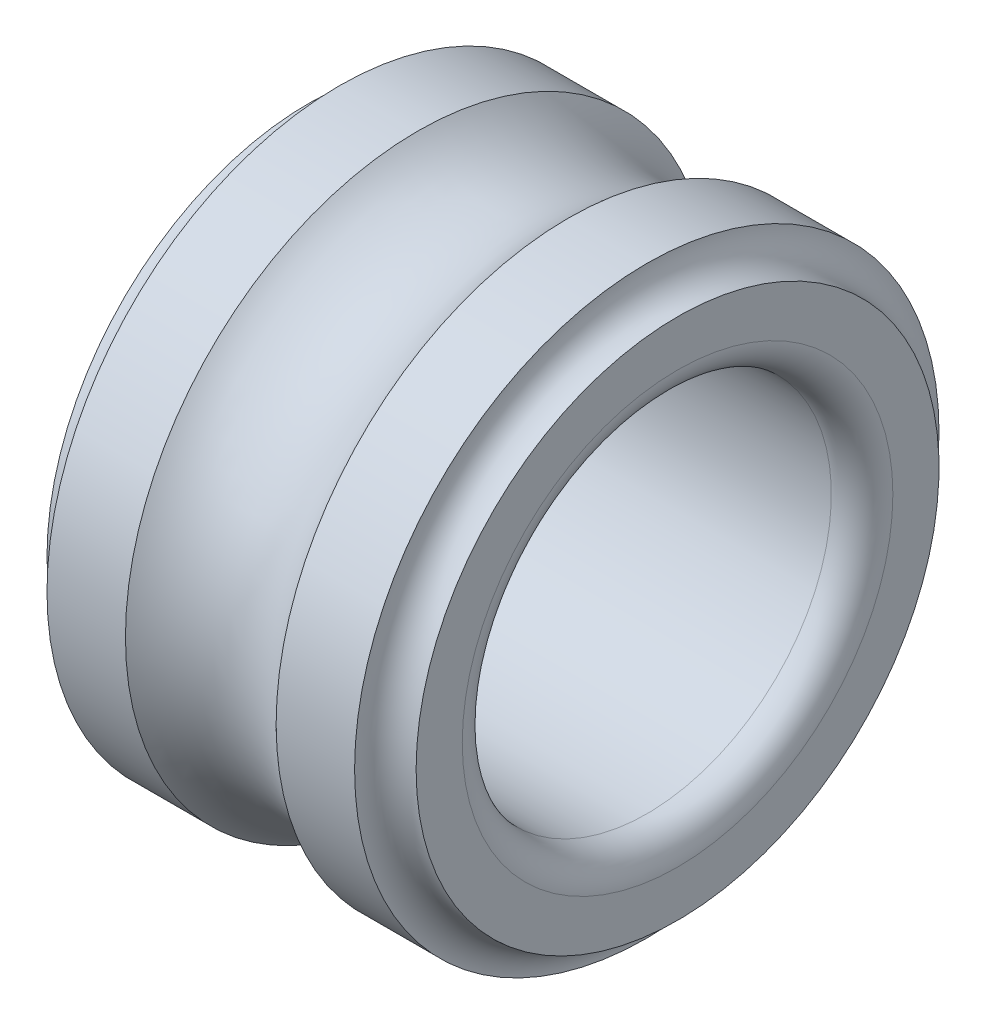
SolidWorks part; units mm, degrees
ref_plane "Front" through (0, 0, 0) normal (0, 0, 1) x (1, 0, 0)
ref_plane "Top" through (0, 0, 0) normal (0, 1, 0) x (1, 0, 0)
ref_plane "Right" through (0, 0, 0) normal (1, 0, 0) x (0, 0, -1)
sketch "Sketch1" plane through (0, 0, 0) normal (0, 0, 1) x (1, 0, 0)
  line L0 (-6, 6) -> (6, 6)
  line L1 (-6, 0) -> (6, 0)
  line L2 (-6, 0) -> (-6, 18)
  line L3 (-6, 18) -> (6, 18)
  line L4 (6, 0) -> (6, 18)
  line L5 (-6, 18) -> (6, 6)
  line L6 (-6, 14.5) -> (6, 14.5)
  line L7 (-6, 9.5) -> (6, 9.5)
  circle A0 centre (0, 12) radius 3.5
  dimension "D4" = 7
  dimension "D1" = 18
  dimension "D2" = 12
  dimension "D3" = 12
  dimension "D5" = 3.5
  dimension "D6" = 3.5
sketch "Sketch2" plane through (0, 0, 0) normal (0, 0, 1) x (1, 0, 0)
  line L0 (-6, 9.5) -> (6, 9.5) construction
  line L1 (-6, 9.5) -> (-2.4495, 9.5)
  line L2 (-6, 6) -> (6, 6) construction
  line L3 (-6, 0) -> (-6, 18) construction
  line L4 (6, 0) -> (6, 18) construction
  line L5 (-6, 0) -> (6, 0) construction
  line L6 (-5, 6) -> (5, 6)
  line L7 (-6, 7) -> (-6, 9.5)
  line L8 (6, 7) -> (6, 9.5)
  line L9 (-6, 0) -> (6, 0) construction
  line L10 (2.4495, 9.5) -> (6, 9.5)
  circle A0 centre (0, 12) radius 3.5 construction
  arc A1 (-2.4495, 9.5) -> (2.4495, 9.5) centre (0, 12) ccw
  arc A2 (5, 6) -> (6, 7) centre (5, 7) ccw
  arc A3 (-5, 6) -> (-6, 7) centre (-5, 7) cw
  dimension "D1" = 1
revolve "Revolve1" add sketch "Sketch2" angle 360 about L9
sketch "Sketch3" plane through (-6, 0, 0) normal (-1, 0, 0) x (0, 0, 1)
  circle A0 centre (0, 0) radius 9.5 construction
  circle A1 centre (0, 0) radius 9.5
  circle A2 centre (0, 0) radius 8.5
  dimension "D1" = 1
extrude "Cut-Extrude1" cut sketch "Sketch3" against normal blind 1
mirror "Mirror1" about plane through (0, 0, 0) normal (1, 0, 0) of "Cut-Extrude1"
fillet "Fillet1" radius 1 2 edges at (5, 0, 8.5) (-5, 0, 8.5)
